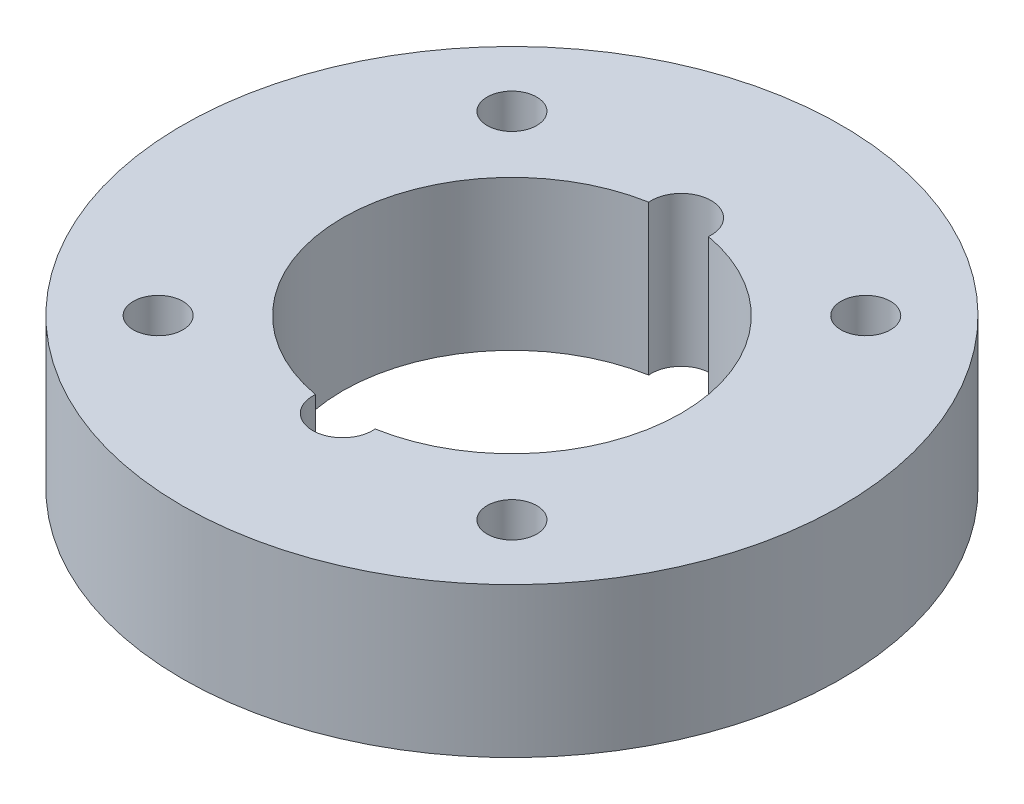
SolidWorks part; units mm, degrees
ref_plane "Front Plane" through (0, 0, 0) normal (0, 0, 1) x (1, 0, 0)
ref_plane "Top Plane" through (0, 0, 0) normal (0, 1, 0) x (1, 0, 0)
ref_plane "Right Plane" through (0, 0, 0) normal (1, 0, 0) x (0, 0, -1)
sketch "0.5in Socket" plane through (0, 0, 0) normal (0, 1, 0) x (1, 0, 0)
  line L0 (0, 0) -> (-14.997, 14.997) construction
  line L1 (14.997, -14.997) -> (0, 0) construction
  line L2 (-14.997, -14.997) -> (0, 0) construction
  line L3 (0, 0) -> (14.997, 14.997) construction
  line L4 (0, 0) -> (0, -14.351) construction
  circle A0 centre (0, 0) radius 27.94
  circle A1 centre (0, 0) radius 2.5527
  arc A2 (-2.53, 14.1262) -> (2.53, 14.1262) centre (0, 14.351) cw
  arc A3 (2.53, 14.1262) -> (2.53, -14.1262) centre (0, 0) cw
  arc A4 (2.53, -14.1262) -> (-2.53, -14.1262) centre (0, -14.351) cw
  arc A5 (-2.53, -14.1262) -> (-2.53, 14.1262) centre (0, 0) cw
  circle A6 centre (14.997, -14.997) radius 2.1
  circle A7 centre (14.997, 14.997) radius 2.1
  circle A8 centre (-14.997, 14.997) radius 2.1
  circle A9 centre (-14.997, -14.997) radius 2.1
  point P4 (0, 0)
  point P8 (0, -14.351)
  point P9 (0, 0)
  point P10 (0, 14.351)
  point P16 (0, 0)
  dimension "D1" = 55.88
  dimension "D2" = 5.1054
  dimension "D4" = 14.351
  dimension "D5" = 14.351
  dimension "D7" = 2.54
  dimension "D8" = 2.54
  dimension "D9" = 4.2
  dimension "D10" = 4.2
  dimension "D11" = 4.2
  dimension "D12" = 4.2
  dimension "D13" = 21.209
  dimension "D17" = 90
  dimension "D3" = 28.702
  dimension "D6" = 14.351
  dimension "D14" = 21.209
  dimension "D15" = 21.209
  dimension "D16" = 21.209
  dimension "D18" = 90
  dimension "D19" = 90
  dimension "D20" = 45
extrude "Boss-Extrude1" add sketch "0.5in Socket" along normal blind 12.7 contours A0 A9 A8 A7 A6 A4 A5 A2 A3 region at (-27.1497, 0, 0)
